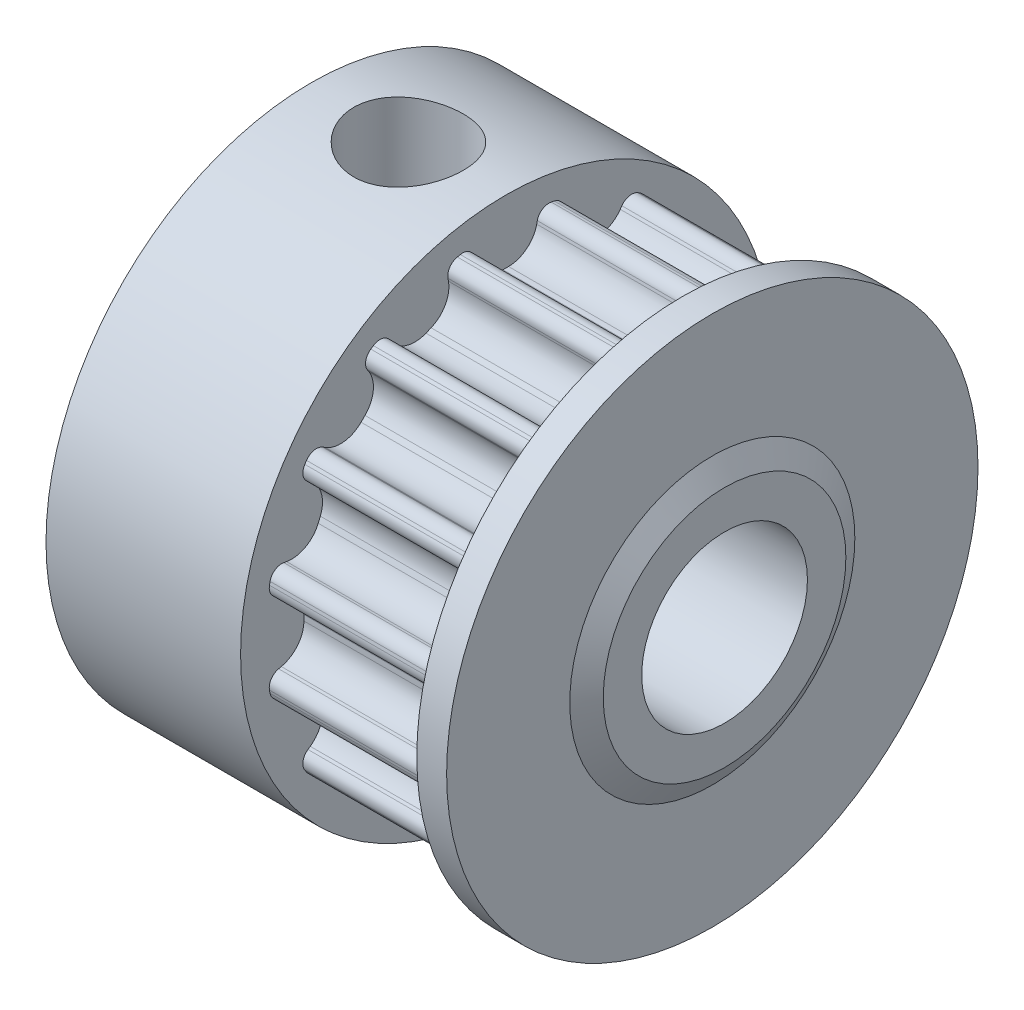
SolidWorks part; units mm, degrees
ref_plane "Face" through (0, 0, 0) normal (0, 0, 1) x (1, 0, 0)
ref_plane "Dessus" through (0, 0, 0) normal (0, 1, 0) x (1, 0, 0)
ref_plane "Droite" through (0, 0, 0) normal (1, 0, 0) x (0, 0, -1)
sketch "Schizzo2" plane through (0, 0, 0) normal (1, 0, 0) x (0, 0, -1)
  line L48 (6.09, -0.0835) -> (6.09, 0.0835)
  line L49 (5.6584, 2.2534) -> (5.5945, 2.4077)
  line L50 (4.3653, 4.2472) -> (4.2472, 4.3653)
  line L51 (2.4077, 5.5945) -> (2.2534, 5.6584)
  line L52 (0.0835, 6.09) -> (-0.0835, 6.09)
  line L53 (-2.2534, 5.6584) -> (-2.4077, 5.5945)
  line L54 (-4.2472, 4.3653) -> (-4.3653, 4.2472)
  line L55 (-5.5945, 2.4077) -> (-5.6584, 2.2534)
  line L56 (-6.09, 0.0835) -> (-6.09, -0.0835)
  line L57 (-5.6584, -2.2534) -> (-5.5945, -2.4077)
  line L58 (-4.3653, -4.2472) -> (-4.2472, -4.3653)
  line L59 (-2.4077, -5.5945) -> (-2.2534, -5.6584)
  line L60 (-0.0835, -6.09) -> (0.0835, -6.09)
  line L61 (2.2534, -5.6584) -> (2.4077, -5.5945)
  line L62 (4.2472, -4.3653) -> (4.3653, -4.2472)
  line L63 (5.5945, -2.4077) -> (5.6584, -2.2534)
  line L64 (-0.9329, 6.7717) -> (-0.9511, 6.8539)
  line L65 (-1.7442, 6.6961) -> (-1.7296, 6.6132)
  line L66 (-3.4533, 5.8992) -> (-3.5015, 5.9682)
  line L67 (-4.1739, 5.5189) -> (-4.1287, 5.448)
  line L68 (-5.448, 4.1287) -> (-5.5189, 4.1739)
  line L69 (-5.9682, 3.5015) -> (-5.8992, 3.4533)
  line L70 (-6.6132, 1.7296) -> (-6.6961, 1.7442)
  line L71 (-6.8539, 0.9511) -> (-6.7717, 0.9329)
  line L72 (-6.7717, -0.9329) -> (-6.8539, -0.9511)
  line L73 (-6.6961, -1.7442) -> (-6.6132, -1.7296)
  line L74 (1.7296, 6.6132) -> (1.7442, 6.6961)
  line L75 (0.9511, 6.8539) -> (0.9329, 6.7717)
  line L76 (4.1287, 5.448) -> (4.1739, 5.5189)
  line L77 (3.5015, 5.9682) -> (3.4533, 5.8992)
  line L78 (5.8992, 3.4533) -> (5.9682, 3.5015)
  line L79 (5.5189, 4.1739) -> (5.448, 4.1287)
  line L80 (6.7717, 0.9329) -> (6.8539, 0.9511)
  line L81 (6.6961, 1.7442) -> (6.6132, 1.7296)
  line L82 (6.6132, -1.7296) -> (6.6961, -1.7442)
  line L83 (6.8539, -0.9511) -> (6.7717, -0.9329)
  line L84 (5.448, -4.1287) -> (5.5189, -4.1739)
  line L85 (5.9682, -3.5015) -> (5.8992, -3.4533)
  line L86 (3.4533, -5.8992) -> (3.5015, -5.9682)
  line L87 (4.1739, -5.5189) -> (4.1287, -5.448)
  line L88 (0.9329, -6.7717) -> (0.9511, -6.8539)
  line L89 (1.7442, -6.6961) -> (1.7296, -6.6132)
  line L90 (-1.7296, -6.6132) -> (-1.7442, -6.6961)
  line L91 (-0.9511, -6.8539) -> (-0.9329, -6.7717)
  line L92 (-4.1287, -5.448) -> (-4.1739, -5.5189)
  line L93 (-3.5015, -5.9682) -> (-3.4533, -5.8992)
  line L94 (-5.8992, -3.4533) -> (-5.9682, -3.5015)
  line L95 (-5.5189, -4.1739) -> (-5.448, -4.1287)
  arc A112 (6.09, -0.0835) -> (6.698, -0.9131) centre (6.96, -0.0835) ccw
  arc A113 (6.698, 0.9131) -> (6.09, 0.0835) centre (6.96, 0.0835) ccw
  arc A114 (5.6584, 2.2534) -> (6.5376, 1.7196) centre (6.4622, 2.5863) ccw
  arc A115 (5.8388, 3.4068) -> (5.5945, 2.4077) centre (6.3983, 2.7406) ccw
  arc A116 (4.3653, 4.2472) -> (5.3819, 4.0906) centre (4.9805, 4.8624) ccw
  arc A117 (4.0906, 5.3819) -> (4.2472, 4.3653) centre (4.8624, 4.9805) ccw
  arc A118 (2.4077, 5.5945) -> (3.4068, 5.8388) centre (2.7406, 6.3983) ccw
  arc A119 (1.7196, 6.5376) -> (2.2534, 5.6584) centre (2.5863, 6.4622) ccw
  arc A120 (0.0835, 6.09) -> (0.9131, 6.698) centre (0.0835, 6.96) ccw
  arc A121 (-0.9131, 6.698) -> (-0.0835, 6.09) centre (-0.0835, 6.96) ccw
  arc A122 (-2.2534, 5.6584) -> (-1.7196, 6.5376) centre (-2.5863, 6.4622) ccw
  arc A123 (-3.4068, 5.8388) -> (-2.4077, 5.5945) centre (-2.7406, 6.3983) ccw
  arc A124 (-4.2472, 4.3653) -> (-4.0906, 5.3819) centre (-4.8624, 4.9805) ccw
  arc A125 (-5.3819, 4.0906) -> (-4.3653, 4.2472) centre (-4.9805, 4.8624) ccw
  arc A126 (-5.5945, 2.4077) -> (-5.8388, 3.4068) centre (-6.3983, 2.7406) ccw
  arc A127 (-6.5376, 1.7196) -> (-5.6584, 2.2534) centre (-6.4622, 2.5863) ccw
  arc A128 (-6.09, 0.0835) -> (-6.698, 0.9131) centre (-6.96, 0.0835) ccw
  arc A129 (-6.698, -0.9131) -> (-6.09, -0.0835) centre (-6.96, -0.0835) ccw
  arc A130 (-5.6584, -2.2534) -> (-6.5376, -1.7196) centre (-6.4622, -2.5863) ccw
  arc A131 (-5.8388, -3.4068) -> (-5.5945, -2.4077) centre (-6.3983, -2.7406) ccw
  arc A132 (-4.3653, -4.2472) -> (-5.3819, -4.0906) centre (-4.9805, -4.8624) ccw
  arc A133 (-4.0906, -5.3819) -> (-4.2472, -4.3653) centre (-4.8624, -4.9805) ccw
  arc A134 (-2.4077, -5.5945) -> (-3.4068, -5.8388) centre (-2.7406, -6.3983) ccw
  arc A135 (-1.7196, -6.5376) -> (-2.2534, -5.6584) centre (-2.5863, -6.4622) ccw
  arc A136 (-0.0835, -6.09) -> (-0.9131, -6.698) centre (-0.0835, -6.96) ccw
  arc A137 (0.9131, -6.698) -> (0.0835, -6.09) centre (0.0835, -6.96) ccw
  arc A138 (2.2534, -5.6584) -> (1.7196, -6.5376) centre (2.5863, -6.4622) ccw
  arc A139 (3.4068, -5.8388) -> (2.4077, -5.5945) centre (2.7406, -6.3983) ccw
  arc A140 (4.2472, -4.3653) -> (4.0906, -5.3819) centre (4.8624, -4.9805) ccw
  arc A141 (5.3819, -4.0906) -> (4.3653, -4.2472) centre (4.9805, -4.8624) ccw
  arc A142 (5.5945, -2.4077) -> (5.8388, -3.4068) centre (6.3983, -2.7406) ccw
  arc A143 (6.5376, -1.7196) -> (5.6584, -2.2534) centre (6.4622, -2.5863) ccw
  arc A144 (-0.9511, 6.8539) -> (-1.3705, 7.1295) centre (-1.3025, 6.7759) ccw
  arc A145 (-1.3705, 7.1295) -> (-1.4621, 7.1112) centre (0, 0) ccw
  arc A146 (-1.4621, 7.1112) -> (-1.7442, 6.6961) centre (-1.3896, 6.7586) ccw
  arc A147 (-1.7196, 6.5376) -> (-1.7296, 6.6132) centre (-2.5863, 6.4622) ccw
  arc A148 (-0.9329, 6.7717) -> (-0.9131, 6.698) centre (-0.0835, 6.96) ccw
  arc A149 (-3.5015, 5.9682) -> (-3.9945, 6.0623) centre (-3.7964, 5.7617) ccw
  arc A150 (-3.9945, 6.0623) -> (-4.0722, 6.0104) centre (0, 0) ccw
  arc A151 (-4.0722, 6.0104) -> (-4.1739, 5.5189) centre (-3.8703, 5.7124) ccw
  arc A152 (-4.0906, 5.3819) -> (-4.1287, 5.448) centre (-4.8624, 4.9805) ccw
  arc A153 (-3.4533, 5.8992) -> (-3.4068, 5.8388) centre (-2.7406, 6.3983) ccw
  arc A154 (-5.5189, 4.1739) -> (-6.0104, 4.0722) centre (-5.7124, 3.8703) ccw
  arc A155 (-6.0104, 4.0722) -> (-6.0623, 3.9945) centre (0, 0) ccw
  arc A156 (-6.0623, 3.9945) -> (-5.9682, 3.5015) centre (-5.7617, 3.7964) ccw
  arc A157 (-5.8388, 3.4068) -> (-5.8992, 3.4533) centre (-6.3983, 2.7406) ccw
  arc A158 (-5.448, 4.1287) -> (-5.3819, 4.0906) centre (-4.9805, 4.8624) ccw
  arc A159 (-6.6961, 1.7442) -> (-7.1112, 1.4621) centre (-6.7586, 1.3896) ccw
  arc A160 (-7.1112, 1.4621) -> (-7.1295, 1.3705) centre (0, 0) ccw
  arc A161 (-7.1295, 1.3705) -> (-6.8539, 0.9511) centre (-6.7759, 1.3025) ccw
  arc A162 (-6.698, 0.9131) -> (-6.7717, 0.9329) centre (-6.96, 0.0835) ccw
  arc A163 (-6.6132, 1.7296) -> (-6.5376, 1.7196) centre (-6.4622, 2.5863) ccw
  arc A164 (-6.8539, -0.9511) -> (-7.1295, -1.3705) centre (-6.7759, -1.3025) ccw
  arc A165 (-7.1295, -1.3705) -> (-7.1112, -1.4621) centre (0, 0) ccw
  arc A166 (-7.1112, -1.4621) -> (-6.6961, -1.7442) centre (-6.7586, -1.3896) ccw
  arc A167 (-6.5376, -1.7196) -> (-6.6132, -1.7296) centre (-6.4622, -2.5863) ccw
  arc A168 (-6.7717, -0.9329) -> (-6.698, -0.9131) centre (-6.96, -0.0835) ccw
  arc A169 (1.7442, 6.6961) -> (1.4621, 7.1112) centre (1.3896, 6.7586) ccw
  arc A170 (1.4621, 7.1112) -> (1.3705, 7.1295) centre (0, 0) ccw
  arc A171 (1.3705, 7.1295) -> (0.9511, 6.8539) centre (1.3025, 6.7759) ccw
  arc A172 (0.9131, 6.698) -> (0.9329, 6.7717) centre (0.0835, 6.96) ccw
  arc A173 (1.7296, 6.6132) -> (1.7196, 6.5376) centre (2.5863, 6.4622) ccw
  arc A174 (4.1739, 5.5189) -> (4.0722, 6.0104) centre (3.8703, 5.7124) ccw
  arc A175 (4.0722, 6.0104) -> (3.9945, 6.0623) centre (0, 0) ccw
  arc A176 (3.9945, 6.0623) -> (3.5015, 5.9682) centre (3.7964, 5.7617) ccw
  arc A177 (3.4068, 5.8388) -> (3.4533, 5.8992) centre (2.7406, 6.3983) ccw
  arc A178 (4.1287, 5.448) -> (4.0906, 5.3819) centre (4.8624, 4.9805) ccw
  arc A179 (5.9682, 3.5015) -> (6.0623, 3.9945) centre (5.7617, 3.7964) ccw
  arc A180 (6.0623, 3.9945) -> (6.0104, 4.0722) centre (0, 0) ccw
  arc A181 (6.0104, 4.0722) -> (5.5189, 4.1739) centre (5.7124, 3.8703) ccw
  arc A182 (5.3819, 4.0906) -> (5.448, 4.1287) centre (4.9805, 4.8624) ccw
  arc A183 (5.8992, 3.4533) -> (5.8388, 3.4068) centre (6.3983, 2.7406) ccw
  arc A184 (6.8539, 0.9511) -> (7.1295, 1.3705) centre (6.7759, 1.3025) ccw
  arc A185 (7.1295, 1.3705) -> (7.1112, 1.4621) centre (0, 0) ccw
  arc A186 (7.1112, 1.4621) -> (6.6961, 1.7442) centre (6.7586, 1.3896) ccw
  arc A187 (6.5376, 1.7196) -> (6.6132, 1.7296) centre (6.4622, 2.5863) ccw
  arc A188 (6.7717, 0.9329) -> (6.698, 0.9131) centre (6.96, 0.0835) ccw
  arc A189 (6.6132, -1.7296) -> (6.5376, -1.7196) centre (6.4622, -2.5863) ccw
  arc A190 (6.6961, -1.7442) -> (7.1112, -1.4621) centre (6.7586, -1.3896) ccw
  arc A191 (7.1112, -1.4621) -> (7.1295, -1.3705) centre (0, 0) ccw
  arc A192 (7.1295, -1.3705) -> (6.8539, -0.9511) centre (6.7759, -1.3025) ccw
  arc A193 (6.698, -0.9131) -> (6.7717, -0.9329) centre (6.96, -0.0835) ccw
  arc A194 (5.5189, -4.1739) -> (6.0104, -4.0722) centre (5.7124, -3.8703) ccw
  arc A195 (6.0104, -4.0722) -> (6.0623, -3.9945) centre (0, 0) ccw
  arc A196 (6.0623, -3.9945) -> (5.9682, -3.5015) centre (5.7617, -3.7964) ccw
  arc A197 (5.8388, -3.4068) -> (5.8992, -3.4533) centre (6.3983, -2.7406) ccw
  arc A198 (5.448, -4.1287) -> (5.3819, -4.0906) centre (4.9805, -4.8624) ccw
  arc A199 (3.5015, -5.9682) -> (3.9945, -6.0623) centre (3.7964, -5.7617) ccw
  arc A200 (3.9945, -6.0623) -> (4.0722, -6.0104) centre (0, 0) ccw
  arc A201 (4.0722, -6.0104) -> (4.1739, -5.5189) centre (3.8703, -5.7124) ccw
  arc A202 (4.0906, -5.3819) -> (4.1287, -5.448) centre (4.8624, -4.9805) ccw
  arc A203 (3.4533, -5.8992) -> (3.4068, -5.8388) centre (2.7406, -6.3983) ccw
  arc A204 (0.9511, -6.8539) -> (1.3705, -7.1295) centre (1.3025, -6.7759) ccw
  arc A205 (1.3705, -7.1295) -> (1.4621, -7.1112) centre (0, 0) ccw
  arc A206 (1.4621, -7.1112) -> (1.7442, -6.6961) centre (1.3896, -6.7586) ccw
  arc A207 (1.7196, -6.5376) -> (1.7296, -6.6132) centre (2.5863, -6.4622) ccw
  arc A208 (0.9329, -6.7717) -> (0.9131, -6.698) centre (0.0835, -6.96) ccw
  arc A209 (-1.7442, -6.6961) -> (-1.4621, -7.1112) centre (-1.3896, -6.7586) ccw
  arc A210 (-1.4621, -7.1112) -> (-1.3705, -7.1295) centre (0, 0) ccw
  arc A211 (-1.3705, -7.1295) -> (-0.9511, -6.8539) centre (-1.3025, -6.7759) ccw
  arc A212 (-0.9131, -6.698) -> (-0.9329, -6.7717) centre (-0.0835, -6.96) ccw
  arc A213 (-1.7296, -6.6132) -> (-1.7196, -6.5376) centre (-2.5863, -6.4622) ccw
  arc A214 (-4.1739, -5.5189) -> (-4.0722, -6.0104) centre (-3.8703, -5.7124) ccw
  arc A215 (-4.0722, -6.0104) -> (-3.9945, -6.0623) centre (0, 0) ccw
  arc A216 (-3.9945, -6.0623) -> (-3.5015, -5.9682) centre (-3.7964, -5.7617) ccw
  arc A217 (-3.4068, -5.8388) -> (-3.4533, -5.8992) centre (-2.7406, -6.3983) ccw
  arc A218 (-4.1287, -5.448) -> (-4.0906, -5.3819) centre (-4.8624, -4.9805) ccw
  arc A219 (-5.9682, -3.5015) -> (-6.0623, -3.9945) centre (-5.7617, -3.7964) ccw
  arc A220 (-6.0623, -3.9945) -> (-6.0104, -4.0722) centre (0, 0) ccw
  arc A221 (-6.0104, -4.0722) -> (-5.5189, -4.1739) centre (-5.7124, -3.8703) ccw
  arc A222 (-5.3819, -4.0906) -> (-5.448, -4.1287) centre (-4.9805, -4.8624) ccw
  arc A223 (-5.8992, -3.4533) -> (-5.8388, -3.4068) centre (-6.3983, -2.7406) ccw
extrude "Estrusione-Estrusione1" add sketch "Schizzo2" along normal blind 5.33 separate body
sketch "Schizzo3" plane through (5.33, 0, 0) normal (1, 0, 0) x (0, 0, -1)
  circle A0 centre (0, 0) radius 8.015
  dimension "D1" = 16.03
extrude "Estrusione-Estrusione2" add sketch "Schizzo3" along normal blind 0.9
sketch "Schizzo4" plane through (0, 0, 0) normal (-1, 0, 0) x (0, 0, 1)
  circle A0 centre (0, 0) radius 8
  dimension "D1" = 16
extrude "Estrusione-Estrusione3" add sketch "Schizzo4" along normal blind 5.87
sketch "Schizzo5" plane through (6.23, 0, 0) normal (1, 0, 0) x (0, 0, -1)
  circle A0 centre (0, 0) radius 4.3
  dimension "D1" = 8.6
extrude "Estrusione-Estrusione4" add sketch "Schizzo5" along normal blind 0.37
chamfer "Smusso1" distance 0.37 angle 60 1 edges at (6.6, 0, -4.3) first distance on face at (6.6, 0, -4.3)
sketch "Schizzo6" plane through (6.6, 0, 0) normal (1, 0, 0) x (0, 0, -1)
  circle A0 centre (0, 0) radius 2.5
  dimension "D1" = 5
extrude "Taglio-Estrusione1" cut sketch "Schizzo6" against normal through all
ref_plane "Piano2" through (0, 8, 0) normal (0, 1, 0) x (1, 0, 0)
hole_wizard "Foro filettato M4x0.7-1" positions "Schizzo8" profile "Schizzo7" tap size "M4x0.7" standard "Ansi Metric" end condition up to next
sketch "Schizzo8" plane through (0, 8, 0) normal (0, 1, 0) x (1, 0, 0)
  line L1 (0, 0) -> (-2.935, 0) construction
  line L2 (-2.935, 0) -> (-5.87, 0) construction
  line L3 (-5.87, -8) -> (-5.87, 8) construction
  point P0 (-2.935, 0)
sketch "Schizzo7" plane through (-2.935, 8, 0) normal (1, 0, 0) x (0, 0, 1)
  line L0 (0, 0) -> (0, 5.5)
  line L1 (0, 5.5) -> (1.65, 5.5)
  line L2 (1.65, 5.5) -> (1.65, 0)
  line L5 (1.65, 0) -> (0, 0)
  line L11 (0, -6.35) -> (0, 107.95) construction
  dimension "Thru Tap Drill Dia." = 3.3
  dimension "Thru Tap Drill Depth" = 5.5
cosmetic thread "Filettatura del foro1"
